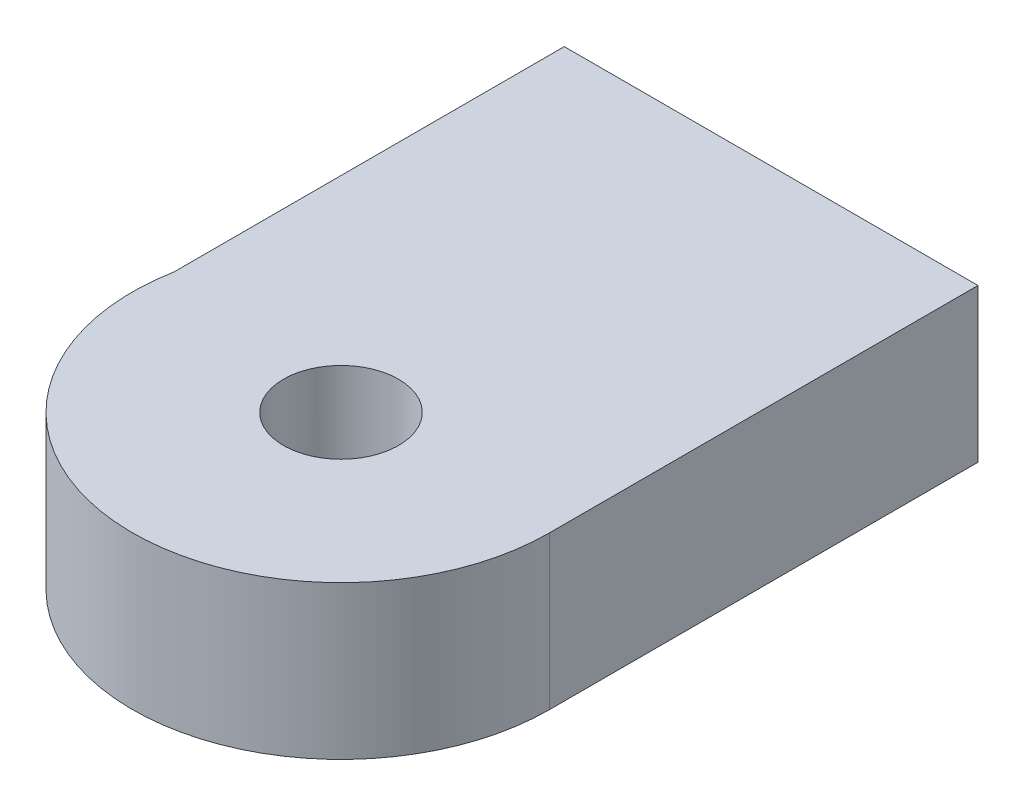
SolidWorks part; units mm, degrees
ref_plane "Front Plane" through (0, 0, 0) normal (0, 0, 1) x (1, 0, 0)
ref_plane "Top Plane" through (0, 0, 0) normal (0, 1, 0) x (1, 0, 0)
ref_plane "Right Plane" through (0, 0, 0) normal (1, 0, 0) x (0, 0, -1)
sketch "Sketch2" plane through (0, -2111.3899, 0) normal (0, 1, 0) x (1, 0, 0)
  circle A1 centre (-53.694, 163.8403) radius 12.7
extrude "Boss-Extrude6" add sketch "Sketch2" along normal blind 40.64
sketch "Sketch3" plane through (0, -2070.7499, 0) normal (0, 1, 0) x (1, 0, 0)
  circle A0 centre (-53.694, 163.8403) radius 3.5
  dimension "D1" = 7
extrude "Cut-Extrude1" cut sketch "Sketch3" against normal up to surface (40.64 mm away) up to face at (-66.394, -2111.3899, -163.8403)
sketch "Sketch4" plane through (0, -2111.3899, 0) normal (0, -1, 0) x (1, 0, 0)
  circle A0 centre (-61.9429, -159.0778) radius 1.778
  circle A2 centre (-53.694, -173.3653) radius 1.778
  circle A3 centre (-45.4451, -159.0778) radius 1.778
extrude "Cut-Extrude2" cut sketch "Sketch4" against normal blind 6
sketch "Sketch7" plane through (0, -2111.3899, 0) normal (0, -1, 0) x (1, 0, 0)
  line L9 (-40.994, -163.8403) -> (-40.994, -182.6343)
  line L10 (-40.994, -182.6343) -> (-66.1797, -182.6343)
  line L11 (-66.1797, -166.1636) -> (-66.1797, -182.6343)
  circle A0 centre (-53.694, -163.8403) radius 12.7 construction
  arc A1 (-66.1797, -166.1636) -> (-40.994, -163.8403) centre (-53.694, -163.8403) ccw
extrude "Boss-Extrude8" add sketch "Sketch7" against normal blind 10
sketch "Sketch8" plane through (0, 0, -182.6343) normal (0, 0, -1) x (-1, 0, 0)
  line L0 (40.994, -2101.3899) -> (40.994, -2111.3899) construction
  line L1 (40.994, -2101.3899) -> (66.1797, -2101.3899)
  line L2 (40.994, -2101.3899) -> (40.994, -2111.3899)
  line L3 (40.994, -2111.3899) -> (66.1797, -2111.3899)
  line L4 (66.1797, -2101.3899) -> (66.1797, -2111.3899)
  line L5 (66.1797, -2101.3899) -> (40.994, -2101.3899) construction
  line L6 (66.1797, -2111.3899) -> (40.994, -2111.3899) construction
  line L7 (66.1797, -2101.3899) -> (66.1797, -2111.3899) construction
extrude "Boss-Extrude9" add sketch "Sketch8" along normal up to surface (7.2848 mm away)
sketch "Sketch9" plane through (0, -2070.7499, 0) normal (0, 1, 0) x (1, 0, 0)
  line L0 (-40.994, 189.9191) -> (-40.994, 163.8403) construction
  line L2 (-66.1797, 163.8403) -> (-66.1797, 189.9191)
  line L3 (-66.1797, 189.9191) -> (-40.994, 189.9191)
  line L4 (-40.994, 163.8403) -> (-40.994, 189.9191)
  line L5 (-66.1797, 166.1636) -> (-66.1797, 189.9191) construction
  arc A0 (-40.994, 163.8403) -> (-66.1797, 163.8403) centre (-53.5868, 163.8403) ccw
extrude "Boss-Extrude10" add sketch "Sketch9" against normal up to surface (30.64 mm away) up to face at (-53.322, -2101.3899, -180.3317)
hole_wizard "CSK for M3 Flat Head Machine Screw1" positions "Sketch14" profile "Sketch15" countersink size "M3" standard "ANSI Metric"
sketch "Sketch14" plane through (0, 0, -189.9191) normal (0, 0, -1) x (-1, 0, 0)
  point P10 (53.5868, -2075.7499)
  point P12 (62.6264, -2075.7499)
  point P14 (44.5473, -2075.7499)
sketch "Sketch15" plane through (-53.5868, -2075.7499, -189.9191) normal (1, 0, 0) x (0, 1, 0)
  line L0 (0, 0) -> (0, 10)
  line L1 (0, 10) -> (1.7, 8.9785)
  line L2 (1.7, 8.9785) -> (1.7, 1.45)
  line L3 (1.7, 1.45) -> (3.15, 0)
  line L5 (3.15, 0) -> (0, 0)
  line L6 (-1.7, 1.45) -> (-3.15, 0) construction
  line L10 (0, 10) -> (-1.7, 8.9785) construction
  line L11 (0, -6.35) -> (0, 107.95) construction
  dimension "Hole Dia." = 3.4
  dimension "Hole Depth" = 10
  dimension "Near C'Sink Dia." = 6.3
  dimension "Near C'Sink Angle" = 90
  dimension "Drill Angle" = 118
ref_plane "Plane1" through (0, -2091.0699, 0) normal (0, 1, 0) x (1, 0, 0)
mirror "Mirror1" about plane through (0, -2091.0699, 0) normal (0, 1, 0) of "CSK for M3 Flat Head Machine Screw1"
sketch "Sketch25" plane through (0, 0, -189.9191) normal (0, 0, -1) x (-1, 0, 0)
  line L0 (40.994, -2111.3899) -> (40.994, -2070.7499) construction
  line L1 (40.994, -2102.0691) -> (67.7131, -2102.0691)
  line L2 (40.994, -2102.0691) -> (40.994, -2070.7499)
  line L3 (40.994, -2070.7499) -> (67.7131, -2070.7499)
  line L4 (67.7131, -2102.0691) -> (67.7131, -2070.7499)
  point P6 (66.1797, -2070.7499)
  point P8 (66.1797, -2102.0691)
  point P11 (0, 0)
extrude "Cut-Extrude9" cut sketch "Sketch25" against normal through all
